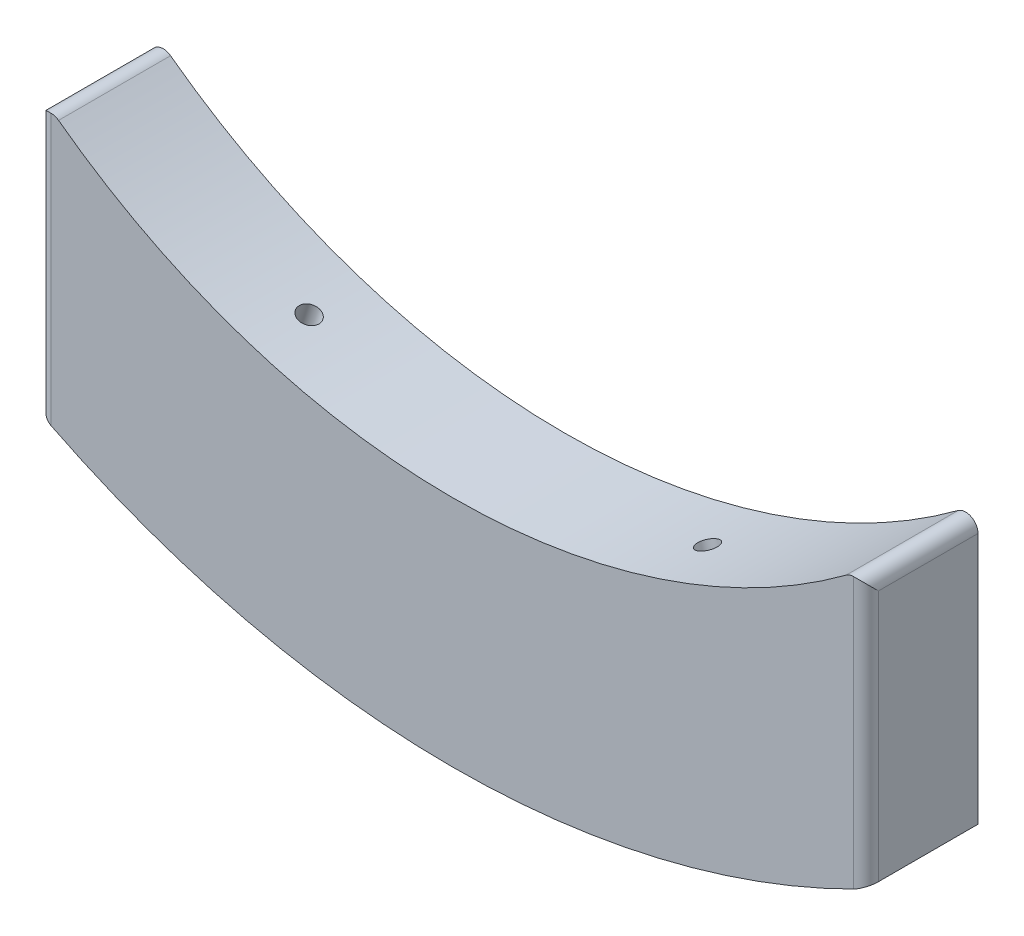
SolidWorks part; units mm, degrees
ref_plane "Front Plane" through (0, 0, 0) normal (0, 0, 1) x (1, 0, 0)
ref_plane "Top Plane" through (0, 0, 0) normal (0, 1, 0) x (1, 0, 0)
ref_plane "Right Plane" through (0, 0, 0) normal (1, 0, 0) x (0, 0, -1)
sketch "Sketch1" plane through (0, 0, 0) normal (0, 0, 1) x (1, 0, 0)
  line L0 (0, 0) -> (0, -50000) construction
  line L1 (0, 0) -> (-66.4918, -127.7296) construction
  line L2 (0, 0) -> (66.4918, -127.7296) construction
  line L3 (66.4918, -127.7296) -> (66.4918, -83.1931)
  line L4 (-66.4918, -127.7296) -> (-66.4918, -83.1931)
  arc A0 (-66.4918, -83.1931) -> (66.4918, -83.1931) centre (0, 0) ccw
  arc A1 (-66.4918, -127.7296) -> (66.4918, -127.7296) centre (0, 0) ccw
  dimension "D1" = 27.5
  dimension "D4" = 144
  dimension "D3" = 106.5
  dimension "D2" = 27.5
extrude "Boss-Extrude1" add sketch "Sketch1" along normal blind 9 and the other way blind 9
hole_wizard "Tap Drill for M4 Tap1" positions "3DSketch1" profile "Sketch2" hole size "M4" standard "DIN"
sketch3d "3DSketch1"
  line L1 (0, 0, 0) -> (0, -144, 0) construction
  line L3 (0, 0, 0) -> (32.0252, -101.5709, 0) construction
  line L6 (0, 0, 0) -> (-32.0252, -101.5709, 0) construction
  line L9 (0, 0, 0) -> (-55.1064, -133.0387, 0) construction
  line L12 (0, 0, 0) -> (55.1064, -133.0387, 0) construction
  line L14 (0, 0, -0.58) -> (0, 0, -50000.58) construction
  point P0 (-32.0252, -101.5709, 0)
  point P3 (32.0252, -101.5709, 0)
  point P6 (-55.1064, -133.0387, 0)
  point P9 (0, -144, 0)
  point P12 (55.1064, -133.0387, 0)
  dimension "D1" = 17.5
  dimension "D2" = 17.5
  dimension "D3" = 22.5
  dimension "D4" = 22.5
sketch "Sketch2" plane through (-32.0252, -101.5709, 0) normal (0, 0, 1) x (-0.9537, 0.3007, 0)
  line L0 (0, 0) -> (0, 25.9914)
  line L1 (0, 25.9914) -> (1.65, 25)
  line L2 (1.65, 25) -> (1.65, 0)
  line L5 (1.65, 0) -> (0, 0)
  line L10 (0, 25.9914) -> (-1.65, 25) construction
  line L11 (0, -6.35) -> (0, 107.95) construction
  dimension "Hole Dia." = 3.3
  dimension "Hole Depth" = 25
  dimension "Drill Angle" = 118
fillet "Fillet2" radius 2 4 edges at (-66.4918, -83.1931, 0) (66.4918, -83.1931, 0) (66.4918, -105.4613, 9) (-66.4918, -105.4613, 9)
